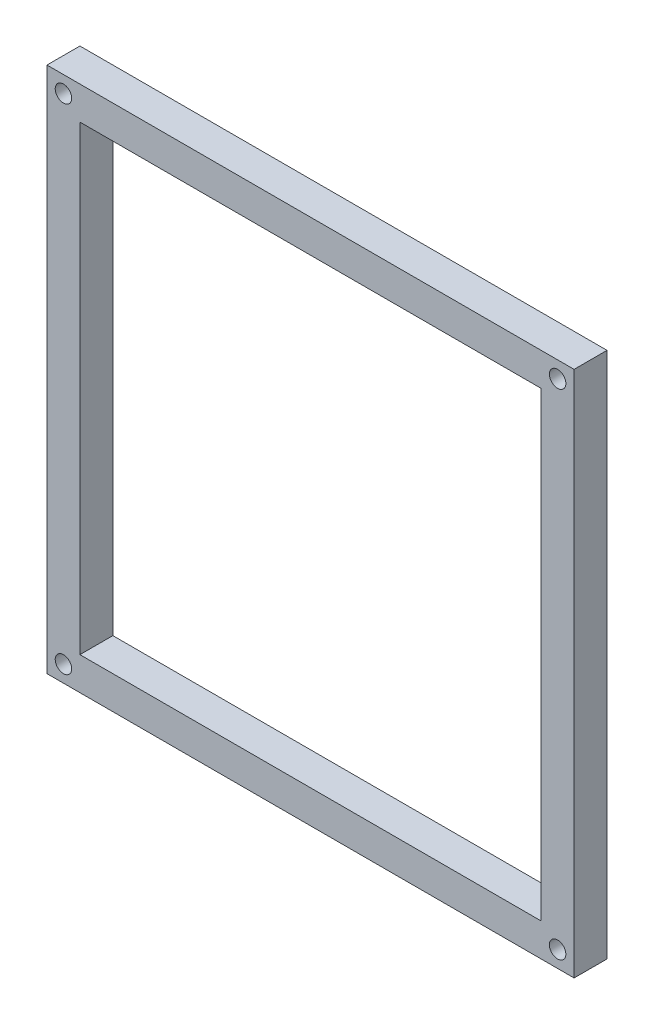
SolidWorks part; units mm, degrees
ref_plane "Alzado" through (0, 0, 0) normal (0, 0, 1) x (1, 0, 0)
ref_plane "Planta" through (0, 0, 0) normal (0, 1, 0) x (1, 0, 0)
ref_plane "Vista lateral" through (0, 0, 0) normal (1, 0, 0) x (0, 0, -1)
sketch "Croquis1" plane through (0, 0, 0) normal (0, 0, 1) x (1, 0, 0)
  line L0 (5, -10) -> (5, 0) construction
  line L1 (0, 0) -> (10, 0)
  line L2 (0, 0) -> (0, -10)
  line L3 (0, -10) -> (10, -10)
  line L4 (10, 0) -> (10, -10)
  line L6 (10, -5) -> (0, -5) construction
  line L7 (4, -10) -> (6, -10)
  line L8 (4, -10) -> (4, -8)
  line L9 (4, -8) -> (6, -8)
  line L10 (6, -10) -> (6, -8)
  line L11 (10, 0) -> (210, 0)
  line L12 (10, 0) -> (10, -10)
  line L13 (10, -10) -> (210, -10)
  line L14 (210, 0) -> (210, -10)
  dimension "D1" = 10
  dimension "D2" = 10
  dimension "D3" = 2
  dimension "D4" = 1
  dimension "D5" = 2
  dimension "D6" = 200
sketch "Croquis2" plane through (0, 0, 0) normal (0, 0, 1) x (1, 0, 0)
  line L0 (10, -10) -> (10, -150)
  line L1 (0, 0) -> (160, 0)
  line L2 (0, 0) -> (0, -160)
  line L3 (0, -160) -> (160, -160)
  line L4 (160, 0) -> (160, -160)
  line L5 (10, -150) -> (150, -150)
  line L6 (150, -10) -> (150, -150)
  line L7 (10, -10) -> (150, -10)
  dimension "D1" = 160
  dimension "D2" = 160
  dimension "D3" = 10
extrude "Saliente-Extruir1" add sketch "Croquis2" along normal blind 10
sketch "Croquis4" plane through (0, 0, 10) normal (0, 0, 1) x (1, 0, 0)
  line L1 (0, 0) -> (10, 0)
  line L2 (0, 0) -> (0, -10)
  line L3 (0, -10) -> (10, -10)
  line L4 (10, 0) -> (10, -10)
  line L5 (160, 0) -> (150, 0)
  line L6 (160, 0) -> (160, -10)
  line L7 (160, -10) -> (150, -10)
  line L8 (150, 0) -> (150, -10)
  line L9 (150, -150) -> (160, -150)
  line L10 (150, -150) -> (150, -160)
  line L11 (150, -160) -> (160, -160)
  line L12 (160, -150) -> (160, -160)
  line L13 (10, -150) -> (0, -150)
  line L14 (10, -150) -> (10, -160)
  line L15 (10, -160) -> (0, -160)
  line L16 (0, -150) -> (0, -160)
extrude "Saliente-Extruir2" add sketch "Croquis4" along normal blind 140 and the other way blind 10
sketch "Croquis7" plane through (0, 0, 150) normal (0, 0, 1) x (1, 0, 0)
  line L1 (0, 0) -> (160, 0)
  line L2 (0, 0) -> (0, -160)
  line L3 (0, -160) -> (160, -160)
  line L4 (160, 0) -> (160, -160)
  line L5 (10, -10) -> (150, -10)
  line L6 (10, -10) -> (10, -150)
  line L7 (10, -150) -> (150, -150)
  line L8 (150, -10) -> (150, -150)
extrude "Saliente-Extruir3" add sketch "Croquis7" along normal blind 10
ref_plane "PlanoX" through (0, 0, 80) normal (0, 0, 1) x (1, 0, 0)
ref_plane "PlanoY" through (0, -80, 0) normal (0, 1, 0) x (1, 0, 0)
ref_plane "PlanoZ" through (80, 0, 0) normal (1, 0, 0) x (0, 0, -1)
ref_axis "EjeXY" through (-11, -80, 80) along (1, 0, 0)
ref_axis "EjeYZ" through (80, -80, -11) along (0, 0, 1)
ref_axis "EjeXZ" through (80, 11, 80) along (0, -1, 0)
sketch "Croquis8" plane through (0, 0, 160) normal (0, 0, 1) x (1, 0, 0)
  line L0 (0, -80) -> (160, -80) construction
  line L1 (0, 0) -> (0, -160) construction
  line L2 (160, -160) -> (160, 0) construction
  line L3 (63, -80) -> (63, -74) construction
  line L4 (80, -121) -> (80, 121) construction
  line L5 (63, -74) -> (0, -74)
  line L6 (63, -74) -> (63, -86)
  line L7 (63, -86) -> (0, -86)
  line L8 (0, -74) -> (0, -86)
  line L9 (97, -86) -> (160, -86)
  line L10 (160, -74) -> (160, -86)
  line L11 (97, -74) -> (160, -74)
  line L12 (97, -74) -> (97, -86)
  circle A0 centre (55, -80) radius 2.5
  circle A1 centre (105, -80) radius 2.5
  point P8 (80, -80)
  dimension "D1" = 5
  dimension "D2" = 25
  dimension "D3" = 8
  dimension "D4" = 6
  dimension "D5" = 12
extrude "Saliente-Extruir4" add sketch "Croquis8" against normal blind 5
sketch "Croquis9" plane through (0, 0, 0) normal (-1, 0, 0) x (0, 0, 1)
  line L0 (10, -10) -> (10, 5.314) construction
  line L2 (10, 5.314) -> (184.1677, 5.314)
  line L3 (10, 5.314) -> (10, -175.2216)
  line L4 (10, -175.2216) -> (184.1677, -175.2216)
  line L5 (184.1677, 5.314) -> (184.1677, -175.2216)
extrude "Cortar-Extruir2" cut sketch "Croquis9" against normal through all
sketch "Croquis10" plane through (0, 0, 10) normal (0, 0, 1) x (1, 0, 0)
  line L0 (0, 0) -> (10, -10) construction
  line L1 (150, -150) -> (160, -160) construction
  line L3 (5, -5) -> (155, -5)
  line L4 (5, -5) -> (5, -155)
  line L5 (5, -155) -> (155, -155)
  line L6 (155, -5) -> (155, -155)
  circle A0 centre (5, -155) radius 2.5
  circle A1 centre (5, -5) radius 2.5
  circle A2 centre (155, -5) radius 2.5
  circle A3 centre (155, -155) radius 2.5
  dimension "D1" = 5
  dimension "D2" = 5
  dimension "D3" = 5
  dimension "D4" = 5
extrude "Cortar-Extruir3" cut sketch "Croquis10" against normal blind 4 contours A3 | A2 | A1 | A0
